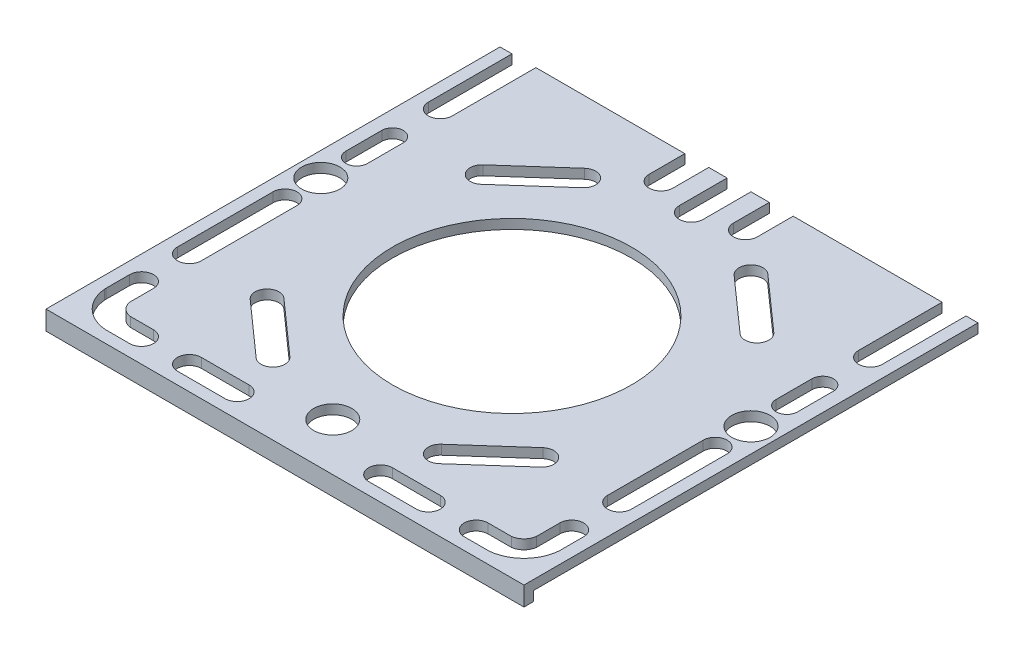
SolidWorks part; units mm, degrees
ref_plane "Front Plane" through (0, 0, 0) normal (0, 0, 1) x (1, 0, 0)
ref_plane "Top Plane" through (0, 0, 0) normal (0, 1, 0) x (1, 0, 0)
ref_plane "Right Plane" through (0, 0, 0) normal (1, 0, 0) x (0, 0, -1)
sketch "Sketch1" plane through (0, 0, 0) normal (0, 1, 0) x (1, 0, 0)
  line L1 (0, 0) -> (200, 0)
  line L2 (0, 0) -> (0, 190)
  line L3 (0, 190) -> (200, 190)
  line L4 (200, 0) -> (200, 190)
  dimension "D1" = 190
  dimension "D2" = 200
extrude "Boss-Extrude1" add sketch "Sketch1" along normal blind 4
sketch "Sketch3" plane through (0, 4, 0) normal (0, 1, 0) x (1, 0, 0)
  line L0 (0, 0) -> (20, 0)
  line L1 (0, 0) -> (200, 0) construction
  line L2 (20, 0) -> (20, 10)
  line L3 (0, 0) -> (0, 20)
  line L4 (0, 190) -> (0, 0) construction
  line L5 (0, 20) -> (10, 20)
  line L6 (10, 20) -> (10, 30) construction
  line L7 (5, 20) -> (5, 30)
  line L8 (15, 20) -> (15, 30)
  line L9 (20, 10) -> (30, 10) construction
  line L10 (20, 15) -> (30, 15)
  line L11 (20, 5) -> (30, 5)
  line L12 (0, 95) -> (200, 95) construction
  line L13 (200, 0) -> (200, 190) construction
  line L14 (100, 0) -> (100, 190) construction
  line L15 (200, 190) -> (0, 190) construction
  line L16 (10, 50) -> (10, 90) construction
  line L17 (5, 50) -> (5, 90)
  line L18 (15, 50) -> (15, 90)
  line L19 (50, 10) -> (70, 10) construction
  line L20 (50, 15) -> (70, 15)
  line L21 (50, 5) -> (70, 5)
  line L22 (190, 50) -> (190, 90) construction
  line L23 (195, 50) -> (195, 90)
  line L24 (185, 50) -> (185, 90)
  line L25 (190, 20) -> (190, 30) construction
  line L26 (195, 20) -> (195, 30)
  line L27 (185, 20) -> (185, 30)
  line L28 (180, 10) -> (170, 10) construction
  line L29 (180, 15) -> (170, 15)
  line L30 (180, 5) -> (170, 5)
  line L31 (150, 10) -> (130, 10) construction
  line L32 (150, 15) -> (130, 15)
  line L33 (150, 5) -> (130, 5)
  line L34 (10, 120) -> (10, 135) construction
  line L37 (157.5, 50) -> (135, 30) construction
  line L40 (154.1782, 53.737) -> (131.6782, 33.737)
  line L43 (160.8218, 46.263) -> (138.3218, 26.263)
  line L46 (157.5, 140) -> (135, 160) construction
  line L49 (154.1782, 136.263) -> (131.6782, 156.263)
  line L52 (160.8218, 143.737) -> (138.3218, 163.737)
  line L55 (5.5, 120) -> (5.5, 135)
  line L58 (200, 95) -> (200, 50) construction
  line L59 (200, 50) -> (0, 50) construction
  line L60 (200, 95) -> (200, 140) construction
  line L61 (200, 140) -> (0, 140) construction
  line L62 (42.5, 140) -> (65, 160) construction
  line L65 (45.8218, 136.263) -> (68.3218, 156.263)
  line L68 (39.1782, 143.737) -> (61.6782, 163.737)
  line L73 (42.5, 50) -> (65, 30) construction
  line L74 (45.8218, 53.737) -> (68.3218, 33.737)
  line L75 (39.1782, 46.263) -> (61.6782, 26.263)
  line L76 (100, 170) -> (100, 190) construction
  line L77 (95, 170) -> (95, 190)
  line L78 (105, 170) -> (105, 190)
  line L79 (82.3355, 175) -> (82.3355, 190) construction
  line L82 (77.3355, 175) -> (77.3355, 190)
  line L85 (10, 155) -> (10, 207.2046) construction
  line L86 (5, 155) -> (5, 207.2046)
  line L87 (15, 155) -> (15, 207.2046)
  line L88 (190, 155) -> (190, 207.2046) construction
  line L89 (195, 155) -> (195, 207.2046)
  line L90 (185, 155) -> (185, 207.2046)
  line L91 (87.3355, 175) -> (87.3355, 190)
  line L92 (117.6645, 175) -> (117.6645, 190) construction
  line L93 (122.6645, 175) -> (122.6645, 190)
  line L94 (112.6645, 175) -> (112.6645, 190)
  line L95 (14.5, 120) -> (14.5, 135)
  line L96 (190, 120) -> (190, 135) construction
  line L97 (194.5, 120) -> (194.5, 135)
  line L98 (185.5, 120) -> (185.5, 135)
  arc A1 (20, 10) -> (9.9962, 20) centre (21.0059, 21.0101) cw construction
  arc A2 (5.0171, 19.5432) -> (19.5451, 5.0207) centre (21.0059, 21.0101) ccw
  arc A3 (14.9753, 20.4568) -> (20.4549, 14.9793) centre (21.0059, 21.0101) ccw
  arc A4 (14.9753, 20.4568) -> (5.0171, 19.5432) centre (9.9962, 20) ccw
  arc A5 (19.5451, 5.0207) -> (20.4549, 14.9793) centre (20, 10) ccw
  arc A6 (5, 20) -> (15, 20) centre (10, 20) ccw
  arc A7 (15, 30) -> (5, 30) centre (10, 30) ccw
  arc A8 (20, 15) -> (20, 5) centre (20, 10) ccw
  arc A9 (30, 5) -> (30, 15) centre (30, 10) ccw
  arc A10 (5, 50) -> (15, 50) centre (10, 50) ccw
  arc A11 (15, 90) -> (5, 90) centre (10, 90) ccw
  arc A12 (50, 15) -> (50, 5) centre (50, 10) ccw
  arc A13 (70, 5) -> (70, 15) centre (70, 10) ccw
  arc A14 (195, 50) -> (185, 50) centre (190, 50) cw
  arc A15 (185, 90) -> (195, 90) centre (190, 90) cw
  arc A16 (195, 20) -> (185, 20) centre (190, 20) cw
  arc A17 (185, 30) -> (195, 30) centre (190, 30) cw
  arc A18 (180, 10) -> (190.0038, 20) centre (178.9941, 21.0101) ccw construction
  arc A19 (194.9829, 19.5432) -> (180.4549, 5.0207) centre (178.9941, 21.0101) cw
  arc A20 (185.0247, 20.4568) -> (179.5451, 14.9793) centre (178.9941, 21.0101) cw
  arc A21 (185.0247, 20.4568) -> (194.9829, 19.5432) centre (190.0038, 20) cw
  arc A22 (180.4549, 5.0207) -> (179.5451, 14.9793) centre (180, 10) cw
  arc A23 (180, 15) -> (180, 5) centre (180, 10) cw
  arc A24 (170, 5) -> (170, 15) centre (170, 10) cw
  arc A25 (150, 15) -> (150, 5) centre (150, 10) cw
  arc A26 (130, 5) -> (130, 15) centre (130, 10) cw
  circle A31 centre (100, 95) radius 50
  arc A44 (154.1782, 53.737) -> (160.8218, 46.263) centre (157.5, 50) cw
  arc A63 (45.8218, 53.737) -> (39.1782, 46.263) centre (42.5, 50) ccw
  arc A64 (61.6782, 26.263) -> (68.3218, 33.737) centre (65, 30) ccw
  arc A65 (138.3218, 26.263) -> (131.6782, 33.737) centre (135, 30) cw
  arc A66 (154.1782, 136.263) -> (160.8218, 143.737) centre (157.5, 140) ccw
  arc A67 (138.3218, 163.737) -> (131.6782, 156.263) centre (135, 160) ccw
  arc A68 (45.8218, 136.263) -> (39.1782, 143.737) centre (42.5, 140) cw
  arc A69 (61.6782, 163.737) -> (68.3218, 156.263) centre (65, 160) cw
  arc A70 (95, 170) -> (105, 170) centre (100, 170) ccw
  arc A71 (105, 190) -> (95, 190) centre (100, 190) ccw
  arc A76 (5, 155) -> (15, 155) centre (10, 155) ccw
  arc A77 (15, 207.2046) -> (5, 207.2046) centre (10, 207.2046) ccw
  arc A78 (195, 155) -> (185, 155) centre (190, 155) cw
  arc A79 (185, 207.2046) -> (195, 207.2046) centre (190, 207.2046) cw
  arc A80 (77.3355, 175) -> (87.3355, 175) centre (82.3355, 175) ccw
  arc A81 (87.3355, 190) -> (77.3355, 190) centre (82.3355, 190) ccw
  arc A82 (122.6645, 175) -> (112.6645, 175) centre (117.6645, 175) cw
  arc A83 (112.6645, 190) -> (122.6645, 190) centre (117.6645, 190) cw
  arc A84 (5.5, 120) -> (14.5, 120) centre (10, 120) ccw
  arc A85 (14.5, 135) -> (5.5, 135) centre (10, 135) ccw
  arc A86 (194.5, 120) -> (185.5, 120) centre (190, 120) cw
  arc A87 (185.5, 135) -> (194.5, 135) centre (190, 135) cw
  point P12 (13.1897, 13.1909)
  point P17 (10, 25)
  point P25 (25, 10)
  point P40 (10, 70)
  point P47 (60, 10)
  point P54 (190, 70)
  point P61 (190, 25)
  point P69 (186.8103, 13.1909)
  point P76 (175, 10)
  point P83 (140, 10)
  point P90 (10, 127.5)
  point P99 (146.25, 40)
  point P106 (146.25, 150)
  point P113 (53.75, 150)
  point P119 (100, 180)
  point P126 (82.3355, 182.5)
  point P133 (117.6645, 182.5)
  point P140 (10, 181.1023)
  point P147 (190, 181.1023)
  point P154 (190, 127.5)
  point P191 (53.75, 40)
  dimension "D4" = 5
  dimension "D8" = 5
  dimension "D11" = 5
  dimension "D16" = 100
  dimension "D19" = 5
  dimension "D22" = 5
  dimension "D24" = 16.0559
  dimension "D29" = 4.5
  dimension "D30" = 20
  dimension "D31" = 5
  dimension "D26" = 5
  dimension "D27" = 5
  dimension "D34" = 35
  dimension "D33" = 30
  dimension "D1" = 20
  dimension "D2" = 20
  dimension "D3" = 10
  dimension "D5" = 5
  dimension "D6" = 10
  dimension "D7" = 10
  dimension "D9" = 40
  dimension "D10" = 20
  dimension "D12" = 20
  dimension "D13" = 20
  dimension "D14" = 5
  dimension "D15" = 30
  dimension "D17" = 35
  dimension "D18" = 0
  dimension "D20" = 42.5
  dimension "D21" = 30
  dimension "D23" = 10
  dimension "D25" = 21.0101
  dimension "D28" = 15
  dimension "D32" = 15
extrude "Cut-Extrude5" cut sketch "Sketch3" against normal blind 10 contours L95 A85 L55 A84 | A26 L33 A25 L32 | A24 L30 A22 A20 L29 | L18 A11 L17 A10 | L8 A7 L7 A4 A3 | L11 A9 L10 A3 A5 | L21 A13 L20 A12 | A20 A21 L26 A17 L27 | L24 A15 L23 A14 | L74 A64 L75 A63 | L40 A65 L43 A44 | A31 | L49 A67 L52 A66 | L65 A69 L68 A68 | A3 A4 A2 A5 | A19 A22 A20 A21 | L91 A81 L82 A80 | L78 A71 L77 A70 | L93 A83 L94 A82 | L87 A76 L86 A77 | L89 A79 L90 A78 | L97 A87 L98 A86 region at (28.9271, 4, -9.9999) region at (10.0014, 4, -28.9271) region at (10, 4, -70) region at (60, 4, -10) region at (189.9986, 4, -28.9271) region at (171.0729, 4, -9.9999) region at (140, 4, -10) region at (10, 4, -127.5)
sketch "Sketch4" plane through (0, 0, 0) normal (0, -1, 0) x (1, 0, 0)
  line L0 (0, -190) -> (0, 0) construction
  line L1 (200, 0) -> (0, 0)
  line L2 (200, 0) -> (200, -4)
  line L3 (200, -4) -> (0, -4)
  line L4 (0, 0) -> (0, -4)
  dimension "D1" = 4
extrude "Boss-Extrude2" add sketch "Sketch4" along normal blind 4
sketch "ｽｹｯﾁ1" plane through (0, 4, 0) normal (0, 1, 0) x (1, 0, 0)
  line L0 (0, 0) -> (200, 0) construction
  line L1 (200, 0) -> (200, 190) construction
  line L2 (0, 190) -> (0, 0) construction
  circle A0 centre (100, 20) radius 8
  circle A1 centre (190, 105) radius 8
  circle A2 centre (10, 105) radius 8
  dimension "D1" = 16
  dimension "D4" = 100
  dimension "D5" = 10
  dimension "D6" = 16
  dimension "D7" = 105
  dimension "D8" = 10
  dimension "D9" = 16
  dimension "D2" = 105
  dimension "D3" = 20
extrude "ｶｯﾄ - 押し出し1" cut sketch "ｽｹｯﾁ1" against normal blind 10
